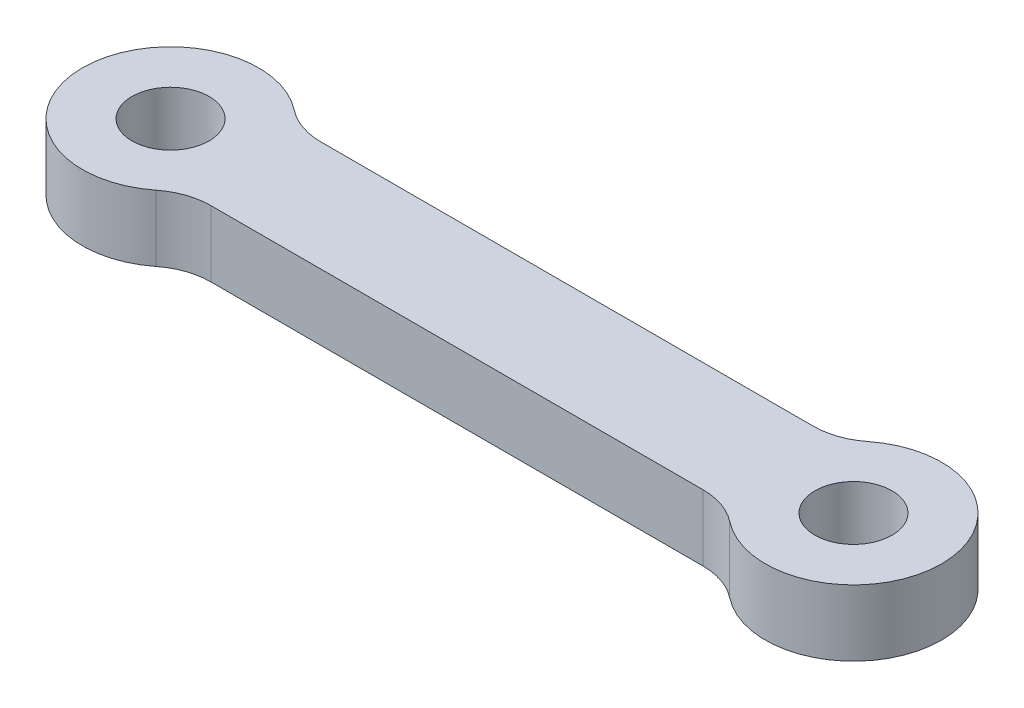
SolidWorks part; units mm, degrees
ref_plane "Front Plane" through (0, 0, 0) normal (0, 0, 1) x (1, 0, 0)
ref_plane "Top Plane" through (0, 0, 0) normal (0, 1, 0) x (1, 0, 0)
ref_plane "Right Plane" through (0, 0, 0) normal (1, 0, 0) x (0, 0, -1)
sketch "Sketch1" plane through (0, 0, 0) normal (0, 1, 0) x (1, 0, 0)
  line L0 (0, 0) -> (31, 0) construction
  line L1 (3.1225, 2.5) -> (27.8775, 2.5)
  line L2 (3.1225, -2.5) -> (27.8775, -2.5)
  circle A0 centre (0, 0) radius 4
  circle A1 centre (31, 0) radius 4
  circle A2 centre (0, 0) radius 1.75
  circle A3 centre (31, 0) radius 1.75
  dimension "D1" = 8
  dimension "D3" = 8
  dimension "D5" = 3.5
  dimension "D6" = 3.5
  dimension "D2" = 31
  dimension "D4" = 2.5
extrude "Boss-Extrude1" add sketch "Sketch1" along normal blind 3 contours A2 A0 | L0 A0 L2 A1 | A0 L0 A1 L1 | A1 A3 region at (3.6675, 0, 1.2873) region at (15.5, 0, -1.2651) region at (15.5, 0, 1.2651) region at (27.3325, 0, -1.2873)
fillet "Fillet1" radius 3 4 edges at (3.1225, 1.5, 2.5) (27.8775, 1.5, 2.5) (27.8775, 1.5, -2.5) (3.1225, 1.5, -2.5)
